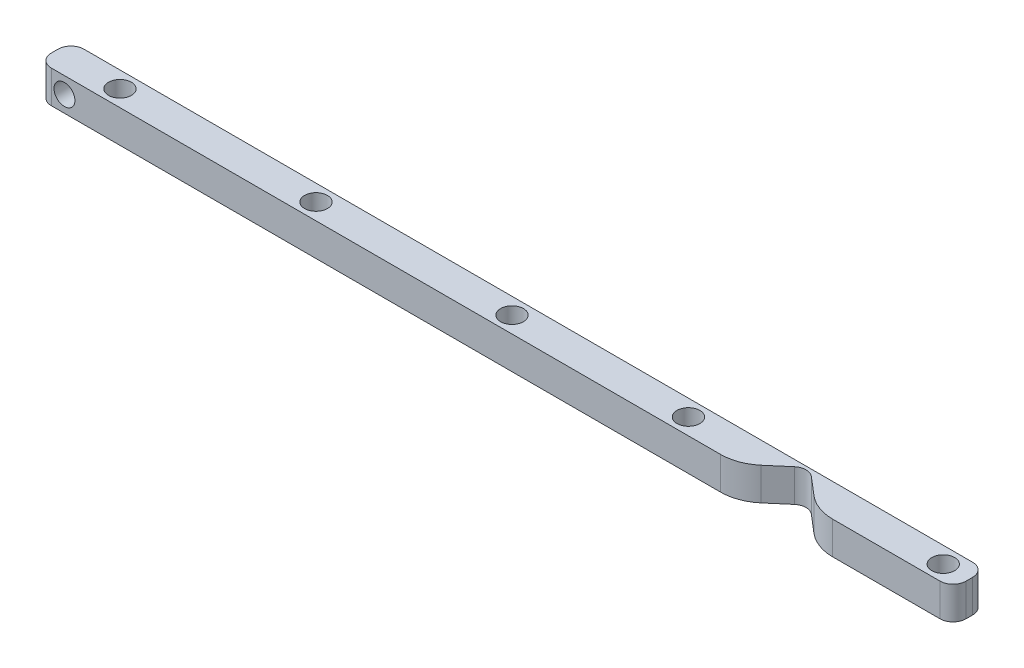
SolidWorks part; units mm, degrees
ref_plane "Front Plane" through (0, 0, 0) normal (0, 0, 1) x (1, 0, 0)
ref_plane "Top Plane" through (0, 0, 0) normal (0, 1, 0) x (1, 0, 0)
ref_plane "Right Plane" through (0, 0, 0) normal (1, 0, 0) x (0, 0, -1)
sketch "Sketch1" plane through (0, 0, 0) normal (0, 1, 0) x (1, 0, 0)
  line L1 (-88.9, 3.175) -> (88.9, 3.175)
  line L2 (-88.9, 3.175) -> (-88.9, -3.175)
  line L3 (-88.9, -3.175) -> (88.9, -3.175)
  line L4 (88.9, 3.175) -> (88.9, -3.175)
  line L5 (-88.9, 3.175) -> (88.9, -3.175) construction
  line L6 (-88.9, -3.175) -> (88.9, 3.175) construction
  point P0 (0, 0)
  dimension "D1" = 6.35
  dimension "D2" = 177.8
extrude "Boss-Extrude1" add sketch "Sketch1" along normal blind 6.35 contours L4 L1 L2 L3 region at (0, 0, 0)
fillet "Fillet1" radius 2.54 4 edges at (88.9, 3.175, -3.175) (88.9, 3.175, 3.175) (-88.9, 3.175, -3.175) (-88.9, 3.175, 3.175)
sketch "Sketch2" plane through (0, 6.35, 0) normal (0, 1, 0) x (1, 0, 0)
  line L0 (-88.9, 0) -> (88.9, 0) construction
  line L1 (-88.9, 0.635) -> (-88.9, -0.635) construction
  line L2 (88.9, 0.635) -> (88.9, -0.635) construction
  circle A0 centre (-76.2, 0) radius 2.2225
  circle A1 centre (83.82, 0) radius 2.2225
  circle A2 centre (34.29, 0) radius 2.2225
  circle A3 centre (-38.1, 0) radius 2.2225
  circle A4 centre (0, 0) radius 2.2225
  dimension "D1" = 4.445
  dimension "D2" = 5.08
  dimension "D3" = 34.29
  dimension "D4" = 38.1
  dimension "D5" = 76.2
extrude "Cut-Extrude1" cut sketch "Sketch2" against normal up to next contours A0 | A3 | A4 | A2 | A1
sketch "Sketch3" plane through (0, 0, 3.175) normal (0, 0, 1) x (1, 0, 0)
  line L0 (-86.36, 6.35) -> (-86.36, 0) construction
  line L1 (-86.36, 3.175) -> (-83.82, 3.175) construction
  circle A0 centre (-83.82, 3.175) radius 2.032
  point P2 (0, 0)
  dimension "D1" = 2.54
  dimension "D2" = 4.064
extrude "Cut-Extrude2" cut sketch "Sketch3" against normal up to next
sketch "Sketch4" plane through (0, 6.35, 0) normal (0, 1, 0) x (1, 0, 0)
  line L0 (52.9591, 1.9303) -> (46.99, -3.175)
  line L1 (-86.36, -3.175) -> (86.36, -3.175) construction
  line L2 (56.2609, 1.9303) -> (62.23, -3.175)
  circle A0 centre (54.61, 0) radius 2.54
  circle A1 centre (83.82, 0) radius 2.2225 construction
  circle A2 centre (83.82, 0) radius 2.2225
  line M12 (-86.36, -3.175) -> (86.36, -3.175)
  dimension "D1" = 5.08
  dimension "D2" = 29.21
  dimension "D3" = 7.62
extrude "Cut-Extrude3" cut sketch "Sketch4" against normal up to next contours A0 L0 L2 M12 | A0 region at (53.4802, 6.35, 2.453)
fillet "Fillet2" radius 8.89 2 edges at (62.23, 3.175, 3.175) (46.99, 3.175, 3.175)
